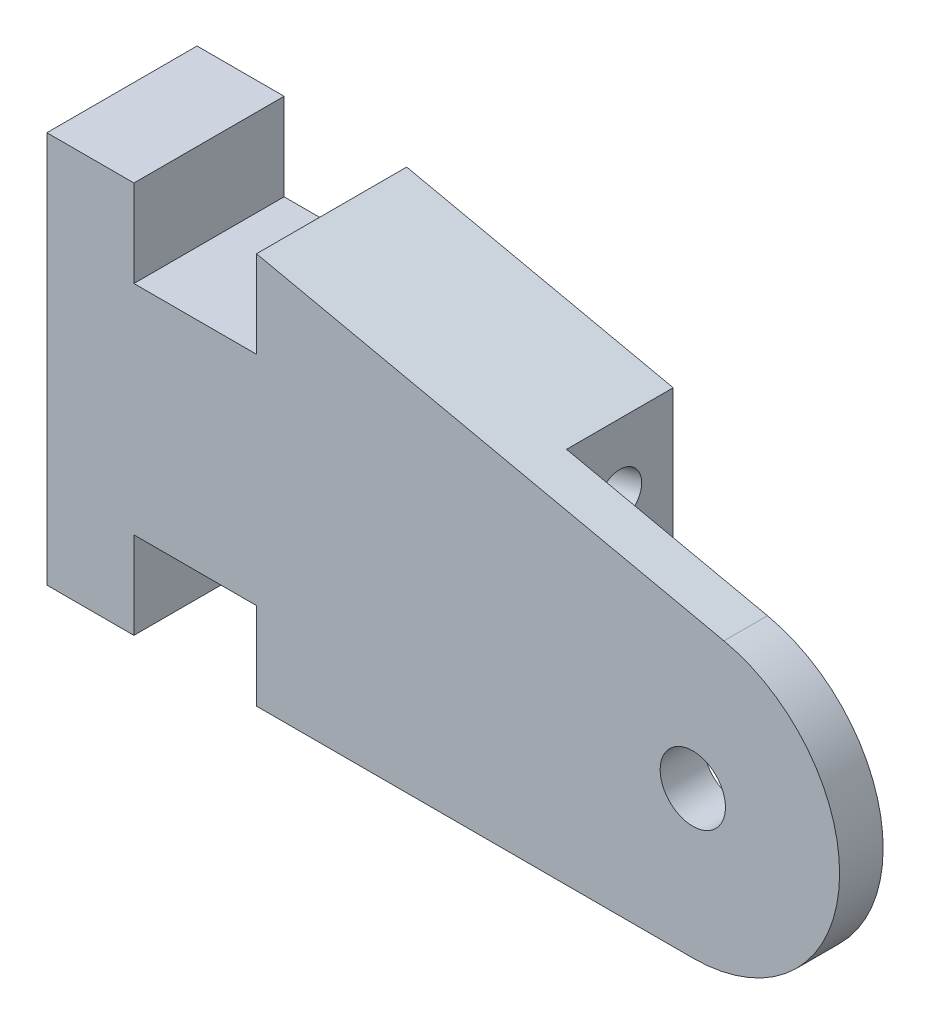
SolidWorks part; units mm, degrees
ref_plane "Front Plane" through (0, 0, 0) normal (0, 0, 1) x (1, 0, 0)
ref_plane "Top Plane" through (0, 0, 0) normal (0, 1, 0) x (1, 0, 0)
ref_plane "Right Plane" through (0, 0, 0) normal (1, 0, 0) x (0, 0, -1)
sketch "Sketch1" plane through (0, 0, 0) normal (0, 0, 1) x (1, 0, 0)
  line L0 (0, 0) -> (0, 18.0003)
  line L1 (9.6315, 0) -> (9.6315, 4)
  line L2 (9.6315, 4) -> (4, 4)
  line L3 (9.6315, 18.0003) -> (31.1079, 13.3365)
  line L4 (9.6315, 18.0003) -> (9.6315, 14.0003)
  line L5 (9.6315, 14.0003) -> (4, 14.0003)
  line L6 (0, 0) -> (4, 0)
  line L7 (4, 0) -> (4, 4)
  line L9 (14.2505, 12.0256) -> (12.2808, 11.6783) construction
  line L10 (7.3568, 10.81) -> (8.225, 5.886) construction
  line L11 (7.3568, 10.81) -> (5.3872, 10.4627) construction
  line L12 (4, 18.0003) -> (4, 14.0003)
  line L13 (0, 18.0003) -> (4, 18.0003)
  line L14 (5.3872, 10.4627) -> (6.2554, 5.5387) construction
  line L15 (6.2554, 5.5387) -> (8.225, 5.886) construction
  line L16 (12.2808, 11.6783) -> (13.1491, 6.7542) construction
  line L17 (13.1491, 6.7542) -> (15.1187, 7.1015) construction
  line L18 (14.2505, 12.0256) -> (15.1187, 7.1015) construction
  line L20 (9.6315, 0) -> (29.6765, 0)
  circle A0 centre (29.6765, 6.745) radius 12.12 construction
  arc A1 (29.6765, 0) -> (31.1079, 13.3365) centre (29.6765, 6.745) ccw
  circle A5 centre (29.6765, 6.745) radius 1.5
  dimension "D1" = 3
  dimension "D2" = 6.745
  dimension "D12" = 24.24
  dimension "D4" = 5.3872
  dimension "D5" = 6.2554
  dimension "D6" = 7.3568
  dimension "D7" = 12.2808
  dimension "D10" = 5.5387
  dimension "D11" = 5.886
  dimension "ThumbLinkLengthMCP" = 20.045
  dimension "D8" = 18.0003
  dimension "D9" = 5.6315
  dimension "D13" = 9.6315
extrude "Boss-Extrude1" add sketch "Sketch1" along normal blind 6.9
sketch "Sketch4" plane through (0, 0, 0) normal (0, 0, 1) x (1, 0, 0)
  line L0 (21.8765, 0) -> (21.8765, 15.3412)
  line L2 (21.8765, 0) -> (29.6765, 0)
  line L3 (9.6315, 0) -> (29.6765, 0) construction
  line L4 (31.1079, 13.3365) -> (9.6315, 18.0003) construction
  line L5 (21.8765, 15.3412) -> (31.1079, 13.3365)
  arc A0 (29.6765, 0) -> (31.1079, 13.3365) centre (29.6765, 6.745) ccw
  dimension "D1" = 21.8765
extrude "Cut-Extrude2" cut sketch "Sketch4" along normal blind 4.9
sketch "Sketch5" plane through (0, 0, 0) normal (-1, 0, 0) x (0, 0, 1)
  line L0 (3.45, 0) -> (3.45, 18.0003) construction
  line L1 (6.9, 0) -> (0, 0) construction
  line L2 (6.9, 18.0003) -> (0, 18.0003) construction
  circle A0 centre (4.45, 8) radius 1 construction
  circle A1 centre (2.45, 8) radius 1
  dimension "D1" = 4.45
  dimension "D3" = 2
  dimension "D2" = 8
extrude "Cut-Extrude3" cut sketch "Sketch5" against normal blind 7
ref_plane "Plane1" through (24.2463, 6.4968, 0) normal (0.9659, 0.2588, 0) x (0, 0, -1)
sketch "Sketch8" plane through (24.2463, 6.4968, 0) normal (0.9659, 0.2588, 0) x (0, 0, -1)
  line L0 (-4.9, -5.662) -> (0, -5.662) construction
  line L1 (-4.9, -5.662) -> (0, -5.662) construction
  line L2 (-2.45, -5.662) -> (-2.45, 6.2012) construction
  circle A0 centre (-2.45, 6.2012) radius 1
  dimension "D1" = 2
  dimension "D2" = 6.2012
  dimension "D3" = 2.45
extrude "Cut-Extrude5" cut sketch "Sketch8" against normal blind 17
equation "\"ThumbLinkLengthMCP@Sketch1\"= \"HB@parametersSketch@prostheticParameters.SLDPRT\" * 0.211"
